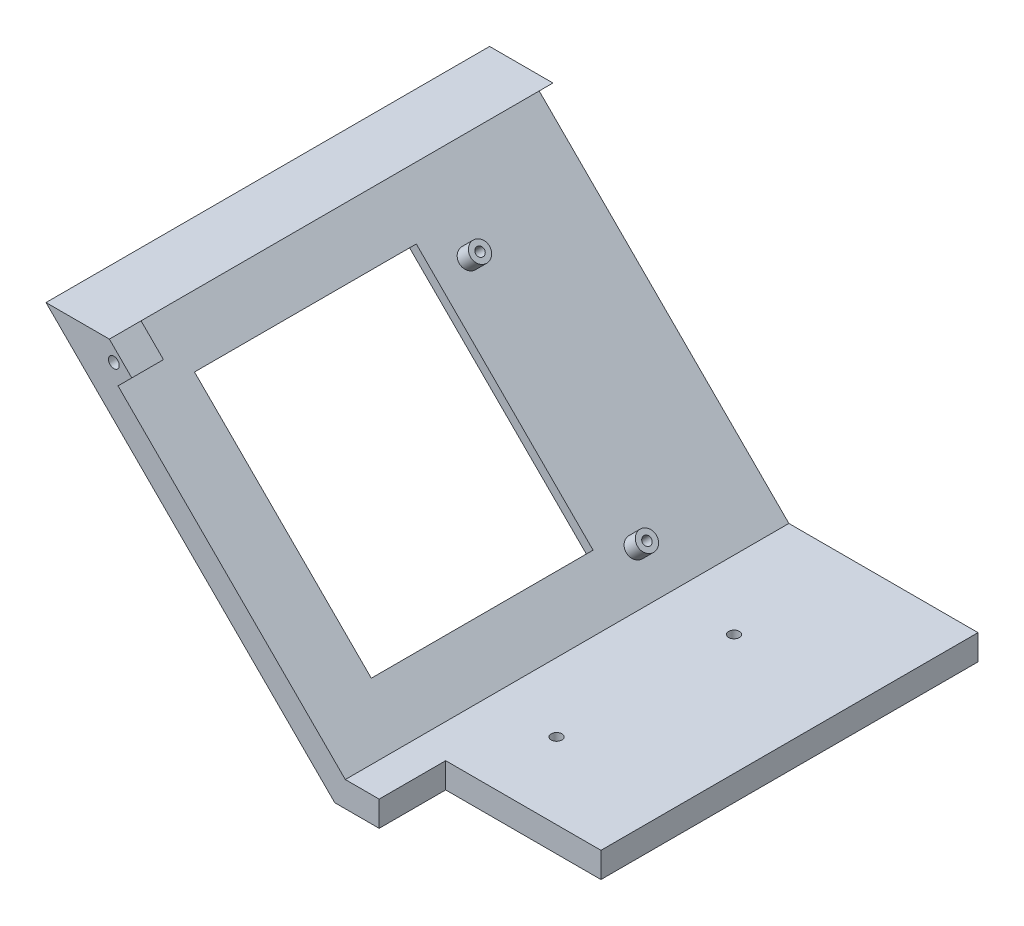
SolidWorks part; units mm, degrees
ref_plane "Plan de face" through (0, 0, 0) normal (0, 0, 1) x (1, 0, 0)
ref_plane "Plan de dessus" through (0, 0, 0) normal (0, 1, 0) x (1, 0, 0)
ref_plane "Plan de droite" through (0, 0, 0) normal (1, 0, 0) x (0, 0, -1)
sketch "Main-Sketch" plane through (0, 0, 0) normal (0, 0, 1) x (1, 0, 0)
  line L0 (0, 0) -> (0, 8)
  line L1 (0, 8) -> (-59.6863, 8)
  line L2 (-59.6863, 8) -> (-138.4931, 86.8069)
  line L3 (-154.15, 91.15) -> (-134.15, 91.15)
  line L4 (-154.15, 91.15) -> (-63, 0)
  line L5 (-63, 0) -> (0, 0)
  line L8 (-134.15, 91.15) -> (-138.4931, 86.8069)
  dimension "D1" = 8
  dimension "D2" = 8
  dimension "D3" = 63
  dimension "D4" = 135
  dimension "D5" = 20
  dimension "D6" = 154.15
extrude "Main-Extrusion" add sketch "Main-Sketch" along normal blind 140
sketch "Lcd-Sketch" plane through (0, 0, 0) normal (0, -1, 0) x (1, 0, 0)
  line L1 (0, 140) -> (-49, 140)
  line L2 (0, 140) -> (0, 119)
  line L3 (0, 119) -> (-49, 119)
  line L4 (-49, 140) -> (-49, 119)
  dimension "D1" = 21
  dimension "D2" = 49
extrude "Lcd-Hole" cut sketch "Lcd-Sketch" against normal through all
sketch "Upp-Fix-Sketch" plane through (0, 0, 140) normal (0, 0, 1) x (1, 0, 0)
  line L0 (-134.15, 91.15) -> (-138.4931, 86.8069)
  line L1 (-138.4931, 86.8069) -> (-131.4221, 79.7358)
  line L2 (-59.6863, 8) -> (-138.4931, 86.8069) construction
  line L3 (-131.4221, 79.7358) -> (-127.0789, 84.0789)
  line L4 (-127.0789, 84.0789) -> (-134.15, 91.15)
  dimension "D1" = 10
extrude "Up-Fix-Extrusion" add sketch "Upp-Fix-Sketch" against normal blind 10
hole_wizard "Fraisage pour vis à tête fraisée M31" positions "Esquisse7" profile "Esquisse6" countersink size "M3" standard "Ansi Metric" end condition up to next
sketch "Esquisse7" plane through (0, 0, 130) normal (0, 0, -1) x (-1, 0, 0)
  line L0 (127.0789, 84.0789) -> (134.15, 91.15) construction
  line L1 (131.4221, 79.7358) -> (127.0789, 84.0789) construction
  point P0 (132.7358, 85.4931)
  dimension "D1" = 3
  dimension "D2" = 5
sketch "Esquisse6" plane through (-132.7358, 85.4931, 130) normal (1, 0, 0) x (0, 1, 0)
  line L0 (0, 0) -> (0, 10)
  line L1 (0, 10) -> (1.7, 10)
  line L2 (1.7, 10) -> (1.7, 1.3)
  line L3 (1.7, 1.3) -> (3, 0)
  line L5 (3, 0) -> (0, 0)
  line L6 (-1.7, 1.3) -> (-3, 0) construction
  line L11 (0, -6.35) -> (0, 107.95) construction
  dimension "Diamètre du perçage jusqu'au prochain" = 3.4
  dimension "Profondeur du perçage jusqu'au prochain" = 10
  dimension "Diamètre du fraisage entrant" = 6
  dimension "Angle du fraisage entrant" = 90
sketch "MotorBoard-Hole-Sketch" plane through (-31.5, -31.5, 0) normal (-0.7071, -0.7071, 0) x (0, 0, 1)
  line L0 (0, 173.4533) -> (0, 44.5477) construction
  line L1 (120, 143.4533) -> (50, 143.4533)
  line L2 (120, 143.4533) -> (120, 64.5477)
  line L3 (120, 64.5477) -> (50, 64.5477)
  line L4 (50, 143.4533) -> (50, 64.5477)
  line L5 (140, 173.4533) -> (140, 44.5477) construction
  line L6 (140, 173.4533) -> (0, 173.4533) construction
  line L7 (140, 44.5477) -> (0, 44.5477) construction
  dimension "D1" = 50
  dimension "D2" = 20
  dimension "D3" = 30
  dimension "D4" = 20
extrude "MotorBoard-Hole" cut sketch "MotorBoard-Hole-Sketch" against normal through all
sketch "MotorBoard-Window-Sketch" plane through (-31.5, -31.5, 0) normal (-0.7071, -0.7071, 0) x (0, 0, 1)
  line L0 (120, 64.5477) -> (120, 143.4533) construction
  line L1 (128, 151.4533) -> (42, 151.4533)
  line L2 (128, 151.4533) -> (128, 56.5477)
  line L3 (128, 56.5477) -> (42, 56.5477)
  line L4 (42, 151.4533) -> (42, 56.5477)
  line L5 (120, 143.4533) -> (50, 143.4533) construction
  line L6 (50, 143.4533) -> (50, 64.5477) construction
  line L7 (50, 64.5477) -> (120, 64.5477) construction
  dimension "D1" = 8
  dimension "D2" = 8
  dimension "D3" = 8
  dimension "D4" = 8
extrude "MotorBoard-Window" cut sketch "MotorBoard-Window-Sketch" against normal blind 5
sketch "MotorBoard-Fix-Sketch" plane through (-25.8431, -25.8431, 0) normal (0.7071, 0.7071, 0) x (0, 0, -1)
  line L0 (-140, 47.8614) -> (-140, 149.3112) construction
  line L1 (-140, 47.8614) -> (0, 47.8614) construction
  circle A0 centre (-39.5, 60.3614) radius 3
  circle A1 centre (-39.5, 134.8614) radius 3
  dimension "D1" = 6
  dimension "D2" = 74.5
  dimension "D3" = 100.5
  dimension "D4" = 12.5
extrude "MotorBoard-Fix-Extrusion" add sketch "MotorBoard-Fix-Sketch" along normal blind 5
sketch "MotorBoard-Fix-Hole-Sketch" plane through (-22.3076, -22.3076, 0) normal (0.7071, 0.7071, 0) x (0, 0, -1)
  circle A0 centre (-39.5, 60.3614) radius 1.35
  circle A1 centre (-39.5, 134.8614) radius 1.35
  circle A2 centre (-39.5, 134.8614) radius 3 construction
  dimension "D1" = 2.7
extrude "MotorBoard-Fix-Hole" cut sketch "MotorBoard-Fix-Hole-Sketch" against normal through all
hole_wizard "Fraisage pour vis à tête fraisée M32" positions "Esquisse8" profile "Esquisse9" countersink size "M3" standard "Ansi Metric" end condition through all
sketch "Esquisse8" plane through (0, 0, 0) normal (0, -1, 0) x (-1, 0, 0)
  line L0 (63, -140) -> (63, 0) construction
  line L2 (63, -140) -> (49, -140) construction
  point P0 (38, -95)
  point P2 (38, -39)
  point P5 (0, 0)
  point P6 (0, 0)
  dimension "D1" = 56
  dimension "D2" = 25
  dimension "D3" = 45
sketch "Esquisse9" plane through (-38, 0, 95) normal (1, 0, 0) x (0, 0, -1)
  line L0 (0, 0) -> (0, 91.15)
  line L1 (0, 91.15) -> (1.7, 91.15)
  line L2 (1.7, 91.15) -> (1.7, 1.45)
  line L3 (1.7, 1.45) -> (3.15, 0)
  line L5 (3.15, 0) -> (0, 0)
  line L6 (-1.7, 1.45) -> (-3.15, 0) construction
  line L11 (0, -6.35) -> (0, 107.95) construction
  dimension "Diamètre du perçage jusqu'au prochain" = 3.4
  dimension "Profondeur du perçage jusqu'au prochain" = 91.15
  dimension "Diamètre du fraisage entrant" = 6.3
  dimension "Angle du fraisage entrant" = 90
